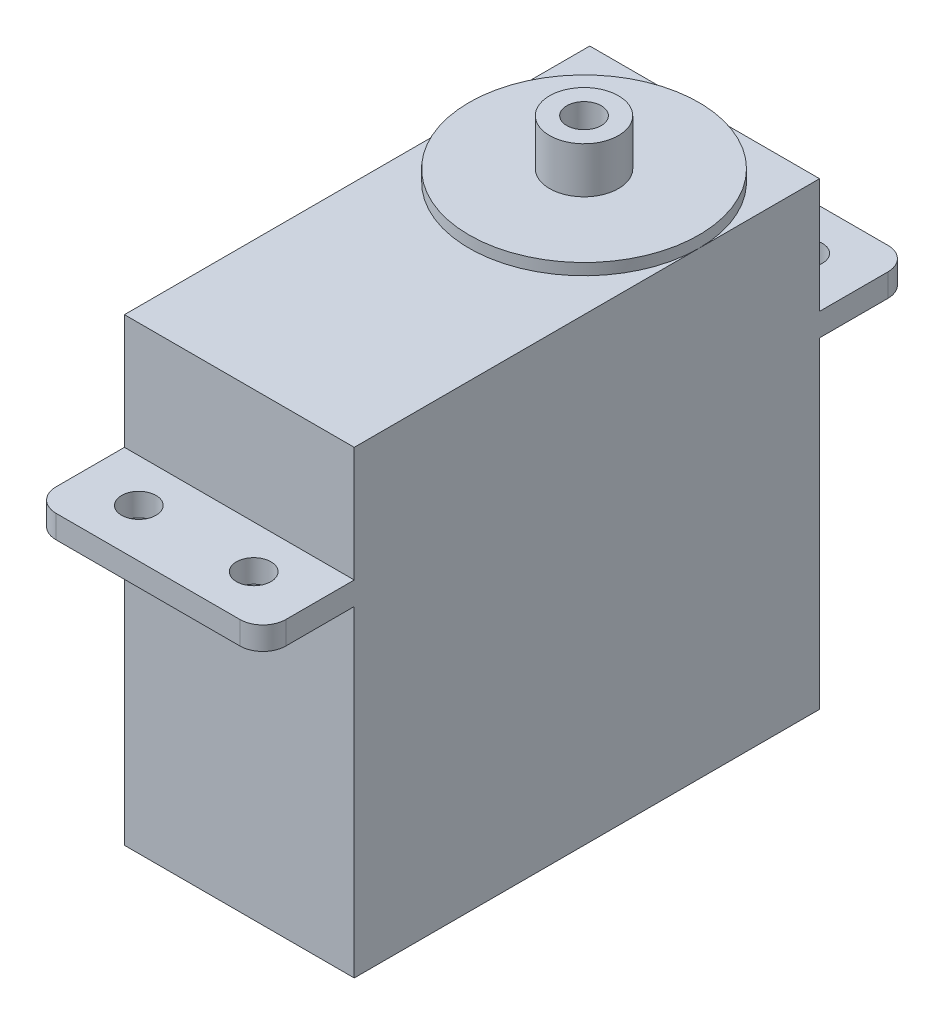
SolidWorks part; units mm, degrees
ref_plane "Front Plane" through (0, 0, 0) normal (0, 0, 1) x (1, 0, 0)
ref_plane "Top Plane" through (0, 0, 0) normal (0, 1, 0) x (1, 0, 0)
ref_plane "Right Plane" through (0, 0, 0) normal (1, 0, 0) x (0, 0, -1)
sketch "Sketch2" plane through (0, 77, 0) normal (0, 1, 0) x (1, 0, 0)
  line L1 (-49.2826, 255.8952) -> (-29.2826, 255.8952)
  line L2 (-49.2826, 255.8952) -> (-49.2826, 296.3952)
  line L3 (-49.2826, 296.3952) -> (-29.2826, 296.3952)
  line L4 (-29.2826, 255.8952) -> (-29.2826, 296.3952)
  dimension "D1" = 40.5
  dimension "D2" = 20
extrude "Boss-Extrude1" add sketch "Sketch2" along normal blind 28
sketch "Sketch3" plane through (0, 105, 0) normal (0, 1, 0) x (1, 0, 0)
  line L0 (-49.2826, 296.3952) -> (-49.2826, 255.8952) construction
  line L1 (-49.2826, 247.9452) -> (-29.2826, 247.9452)
  line L2 (-49.2826, 247.9452) -> (-49.2826, 304.3452)
  line L3 (-49.2826, 304.3452) -> (-29.2826, 304.3452)
  line L4 (-29.2826, 247.9452) -> (-29.2826, 304.3452)
  line L5 (-29.2826, 255.8952) -> (-29.2826, 296.3952) construction
  line L6 (-39.2826, 255.8952) -> (-39.2826, 296.3952) construction
  line L7 (-49.2826, 255.8952) -> (-29.2826, 255.8952) construction
  line L8 (-29.2826, 296.3952) -> (-49.2826, 296.3952) construction
  line L9 (-39.2826, 276.1452) -> (-34.2441, 276.1452) construction
  dimension "D1" = 0
  dimension "D2" = 0
  dimension "D3" = 56.4
  dimension "D4" = 28.2
extrude "Boss-Extrude2" add sketch "Sketch3" along normal blind 2
sketch "Sketch4" plane through (0, 107, 0) normal (0, 1, 0) x (1, 0, 0)
  line L4 (-49.2826, 296.3952) -> (-49.2826, 255.8952)
  line L5 (-29.2826, 296.3952) -> (-49.2826, 296.3952)
  line L6 (-29.2826, 255.8952) -> (-29.2826, 296.3952)
  line L7 (-49.2826, 255.8952) -> (-29.2826, 255.8952)
  line L8 (-49.2826, 296.3952) -> (-49.2826, 255.8952)
  line L9 (-29.2826, 296.3952) -> (-49.2826, 296.3952)
  line L10 (-29.2826, 255.8952) -> (-29.2826, 296.3952)
  line L11 (-49.2826, 255.8952) -> (-29.2826, 255.8952)
  dimension "D1" = 0
extrude "Boss-Extrude3" add sketch "Sketch4" along normal blind 10
sketch "Sketch5" plane through (0, 117, 0) normal (0, 1, 0) x (1, 0, 0)
  line L0 (-29.2826, 255.8952) -> (-29.2826, 296.3952) construction
  line L1 (-49.2826, 296.3952) -> (-49.2826, 255.8952) construction
  line L2 (-49.2826, 255.8952) -> (-29.2826, 255.8952) construction
  circle A0 centre (-39.2826, 285.8952) radius 10
  dimension "D1" = 30
extrude "Boss-Extrude4" add sketch "Sketch5" along normal blind 1
sketch "Sketch6" plane through (0, 118, 0) normal (0, 1, 0) x (1, 0, 0)
  circle A0 centre (-39.2826, 285.8952) radius 3
  circle A1 centre (-39.2826, 285.8952) radius 1.5
extrude "Boss-Extrude5" add sketch "Sketch6" along normal blind 4
sketch "Sketch7" plane through (0, 107, 0) normal (0, 1, 0) x (1, 0, 0)
  line L0 (-39.2826, 247.9452) -> (-39.2826, 304.3452) construction
  line L1 (-49.2826, 247.9452) -> (-29.2826, 247.9452) construction
  line L2 (-29.2826, 304.3452) -> (-49.2826, 304.3452) construction
  line L3 (-39.2826, 276.1452) -> (-49.2826, 276.1452) construction
  line L4 (-49.2826, 285.8952) -> (-49.2826, 255.8952) construction
  circle A0 centre (-44.2826, 252.1452) radius 1.5
  circle A1 centre (-34.2826, 252.1452) radius 1.5
  circle A2 centre (-34.2826, 300.1452) radius 1.5
  circle A3 centre (-44.2826, 300.1452) radius 1.5
  dimension "D1" = 5
  dimension "D2" = 24
extrude "Cut-Extrude1" cut sketch "Sketch7" against normal blind 2
fillet "Fillet1" radius 2 4 edges at (-29.2826, 106, -304.3452) (-49.2826, 106, -304.3452) (-49.2826, 106, -247.9452) (-29.2826, 106, -247.9452)
